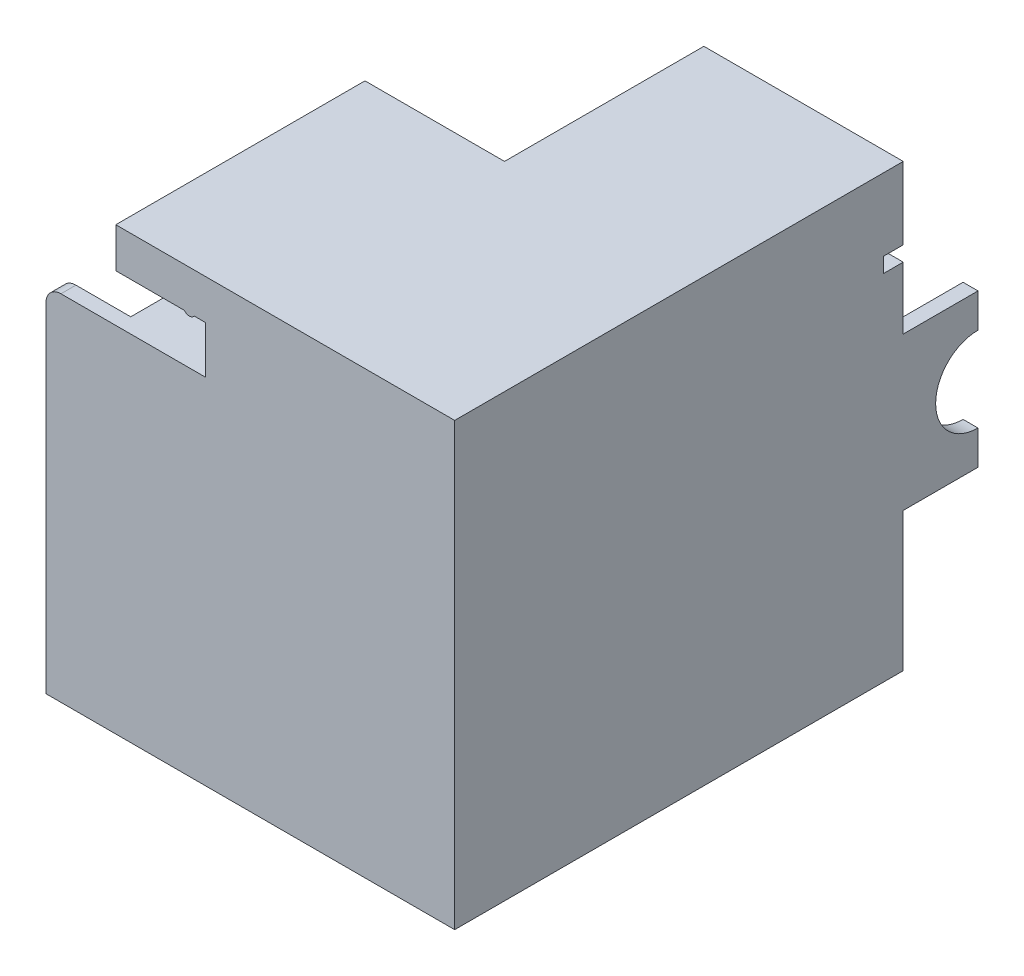
SolidWorks part; units mm, degrees
ref_plane "Front Plane" through (0, 0, 0) normal (0, 0, 1) x (1, 0, 0)
ref_plane "Top Plane" through (0, 0, 0) normal (0, 1, 0) x (1, 0, 0)
ref_plane "Right Plane" through (0, 0, 0) normal (1, 0, 0) x (0, 0, -1)
sketch "Sketch1" plane through (0, 0, 75.0548) normal (0, 0, 1) x (1, 0, 0)
  line L0 (-69.2126, 51.9708) -> (-97.2126, 51.9708)
  line L1 (-97.2126, 51.9708) -> (-97.2126, 43.9708)
  line L2 (-97.2126, 43.9708) -> (-83.4626, 43.9708)
  line L3 (-81.4626, 43.9708) -> (-79.2126, 43.9708)
  line L4 (-79.2126, 43.9708) -> (-79.2126, 34.4708)
  line L5 (-79.2126, 34.4708) -> (-97.2126, 34.4708)
  line L6 (-97.2126, 34.4708) -> (-97.2126, 26.4708)
  line L7 (-97.2126, 26.4708) -> (-69.2126, 26.4708)
  line L8 (-69.2126, 26.4708) -> (-69.2126, 51.9708)
  arc A0 (-83.4626, 43.9708) -> (-81.4626, 43.9708) centre (-82.4626, 44.7208) ccw
  arc A1 (-83.4626, 43.9708) -> (-81.4626, 43.9708) centre (-82.4626, 44.7208) ccw construction
  arc M1 (-83.4626, 43.9708) -> (-81.4626, 43.9708) centre (-82.4626, 44.7208) ccw
  line M2 (-81.4626, 43.9708) -> (-79.2126, 43.9708)
  line M3 (-79.2126, 43.9708) -> (-79.2126, 34.4708)
  line M4 (-79.2126, 34.4708) -> (-97.2126, 34.4708)
  line M5 (-97.2126, 34.4708) -> (-97.2126, 26.4708)
  line M6 (-97.2126, 26.4708) -> (-69.2126, 26.4708)
  line M7 (-69.2126, 26.4708) -> (-69.2126, 51.9708)
  line M8 (-69.2126, 51.9708) -> (-97.2126, 51.9708)
  line M9 (-97.2126, 51.9708) -> (-97.2126, 43.9708)
  line M10 (-97.2126, 43.9708) -> (-83.4626, 43.9708)
extrude "Boss-Extrude1" add sketch "Sketch1" along normal blind 50 contours M10 M1 M2 M3 M4 M5 M6 M7 M8 M9 region at (-69.5913, 39.2208, 75.0548)
sketch "Sketch2" plane through (-69.2126, 0, 0) normal (1, 0, 0) x (0, 0, -1)
  line L0 (-125.0548, 51.9708) -> (-35.0548, 51.9708)
  line L1 (-35.0548, 51.9708) -> (-35.0548, 48.9708)
  line L2 (-35.0548, 22.4708) -> (-35.0548, 51.9708) construction
  line L3 (-35.0548, 48.9708) -> (-125.0548, 48.9708)
  line L4 (-125.0548, 26.4708) -> (-125.0548, 51.9708) construction
  line L5 (-125.0548, 48.9708) -> (-125.0548, 51.9708)
  line L6 (-125.0548, 48.9708) -> (-125.0548, 26.4708)
  line L7 (-125.0548, 26.4708) -> (-122.0548, 26.4708)
  line L8 (-125.0548, 26.4708) -> (-75.0548, 26.4708) construction
  line L9 (-122.0548, 26.4708) -> (-122.0548, 48.9708)
  line M3 (-75.0548, 26.4708) -> (-75.0548, 51.9708)
  line M4 (-75.0548, 51.9708) -> (-125.0548, 51.9708)
  line M5 (-125.0548, 51.9708) -> (-125.0548, 26.4708)
  line M6 (-125.0548, 26.4708) -> (-75.0548, 26.4708)
  dimension "D1" = 3
  dimension "D2" = 3
extrude "Boss-Extrude2" add sketch "Sketch2" along normal up to surface (40 mm away) contours L9 L3 M6 M5 | L3 M3 M4 M5 | L3 L1 L0 M3 region at (-69.2126, 50.4708, 100.0548) region at (-69.2126, 50.4708, 55.0548) region at (-69.2126, 37.7208, 123.5548)
sketch "Sketch3" plane through (0, 0, 75.0548) normal (0, 0, -1) x (-1, 0, 0)
  line L0 (79.2126, 43.9708) -> (97.2126, 43.9708)
  line L1 (97.2126, 43.9708) -> (97.2126, 34.4708)
  line L2 (97.2126, 34.4708) -> (79.2126, 34.4708)
  line L3 (79.2126, 34.4708) -> (79.2126, 43.9708)
extrude "Cut-Extrude1" cut sketch "Sketch3" against normal blind 30
sketch "Sketch4" plane through (0, 48.9708, 0) normal (0, -1, 0) x (1, 0, 0)
  line L0 (-29.2126, 125.0548) -> (-32.2126, 125.0548)
  line L1 (-97.2126, 125.0548) -> (-29.2126, 125.0548) construction
  line L2 (-32.2126, 125.0548) -> (-32.2126, 35.0548)
  line L3 (-29.2126, 35.0548) -> (-69.2126, 35.0548) construction
  line L4 (-32.2126, 35.0548) -> (-29.2126, 35.0548)
  line L5 (-29.2126, 35.0548) -> (-29.2126, 125.0548)
  dimension "D1" = 3
extrude "Boss-Extrude3" add sketch "Sketch4" along normal up to surface (85.5 mm away)
sketch "Sketch6" plane through (-32.2126, 0, 0) normal (-1, 0, 0) x (0, 0, 1)
  line L0 (125.0548, -36.5292) -> (35.0548, -36.5292)
  line L1 (35.0548, -36.5292) -> (35.0548, -33.5292)
  line L2 (35.0548, -36.5292) -> (35.0548, 48.9708) construction
  line L3 (35.0548, -33.5292) -> (125.0548, -33.5292)
  line L4 (125.0548, -36.5292) -> (125.0548, 26.4708) construction
  line L5 (125.0548, -33.5292) -> (125.0548, -36.5292)
  dimension "D1" = 3
extrude "Boss-Extrude4" add sketch "Sketch6" along normal up to surface (79 mm away)
sketch "Sketch7" plane through (0, 0, 125.0548) normal (0, 0, 1) x (1, 0, 0)
  line L0 (-111.2126, -33.5292) -> (-32.2126, -33.5292)
  line L1 (-32.2126, -33.5292) -> (-32.2126, 26.4708)
  line L2 (-32.2126, 26.4708) -> (-97.2126, 26.4708)
  line L3 (-97.2126, 26.4708) -> (-97.2126, 34.4708)
  line L4 (-97.2126, 34.4708) -> (-111.2126, 34.4708)
  line L5 (-111.2126, 34.4708) -> (-111.2126, -33.5292)
extrude "Boss-Extrude5" add sketch "Sketch7" against normal blind 3
fillet "Fillet1" radius 3 1 edges at (-111.2126, 34.4708, 123.5548)
sketch "Sketch11" plane through (-29.2126, 0, 0) normal (1, 0, 0) x (0, 0, -1)
  line L0 (-35.0548, 34.4708) -> (-39.0548, 34.4708)
  line L1 (-35.0548, 51.9708) -> (-35.0548, -36.5292) construction
  line L2 (-35.0548, 28.4708) -> (-35.0548, 34.4708) construction
  line L3 (-39.0548, 34.4708) -> (-39.0548, 37.4708)
  line L4 (-39.0548, 37.4708) -> (-35.0548, 37.4708)
  line L5 (-35.0548, 37.4708) -> (-35.0548, 34.4708)
  line L6 (-75.0548, 34.4708) -> (-25.0548, 34.4708) construction
  point P6 (-35.0548, 36.9436)
  point P9 (0, 0)
  point P10 (-35.0548, 34.4708)
  dimension "D1" = 3
  dimension "D2" = 4
extrude "Cut-Extrude2" cut sketch "Sketch11" against normal up to surface (3 mm away) up to face at (-32.2126, 7.7208, 78.5548)
sketch "Sketch12" plane through (0, -36.5292, 0) normal (0, -1, 0) x (1, 0, 0)
  line L0 (-111.2126, 35.0548) -> (-29.2126, 35.0548)
  line L1 (-69.2126, 35.0548) -> (-69.2126, 75.0548)
  line L2 (-70.7126, 39.0548) -> (-67.7126, 39.0548)
  line L3 (-67.7126, 39.0548) -> (-67.7126, 35.0548)
  line L4 (-67.7126, 35.0548) -> (-70.7126, 35.0548)
  line L5 (-70.7126, 35.0548) -> (-70.7126, 39.0548)
  line L6 (-75.2126, 75.0548) -> (-63.2126, 75.0548)
  circle A0 centre (-75.2126, 75.0548) radius 1.2
  circle A1 centre (-63.2126, 75.0548) radius 1.2
  point P10 (-69.2126, 39.0548)
  point P14 (-69.2126, 75.0548)
  dimension "D5" = 2.4
  dimension "D6" = 2.4
  dimension "D1" = 40
  dimension "D2" = 4
  dimension "D3" = 3
  dimension "D4" = 12
extrude "Cut-Extrude3" cut sketch "Sketch12" against normal up to surface (3 mm away) contours A0 | A1 | L5 L0 L1 L2 | L3 L2 L1 L0 region at (-69.9626, -36.5292, 37.0548) region at (-76.3786, -36.5292, 75.0548) region at (-63.2126, -36.5292, 76.2209) region at (-68.4626, -36.5292, 37.0548) up to face at (-71.7126, -33.5292, 78.5548)
sketch "Sketch13" plane through (-29.2126, 0, 0) normal (1, 0, 0) x (0, 0, -1)
  line L0 (-5.0548, 22.4708) -> (-5.0548, -9.1792)
  line L1 (-5.0548, 6.6458) -> (-20.0548, 6.6458)
  line L2 (-5.0548, 22.4708) -> (-35.0548, 22.4708)
  line L3 (-35.0548, 22.4708) -> (-35.0548, -9.1792)
  line L4 (-35.0548, -9.1792) -> (-5.0548, -9.1792)
  line L5 (-20.0548, -9.1792) -> (-20.0548, 22.4708)
  line L6 (-20.0548, 21.9708) -> (-35.0548, 21.9708)
  line L7 (-20.0548, -8.6792) -> (-35.0548, -8.6792)
  circle A0 centre (-20.0548, 6.6458) radius 8.5
  point P9 (-20.0548, 6.6458)
  dimension "D1" = 17
  dimension "D2" = 15
  dimension "D3" = 0.5
  dimension "D4" = 0.5
extrude "Boss-Extrude6" add sketch "Sketch13" against normal blind 3 contours A0 L5 L6 L3 L7 region at (-29.2126, 6.6458, 28.8306)
